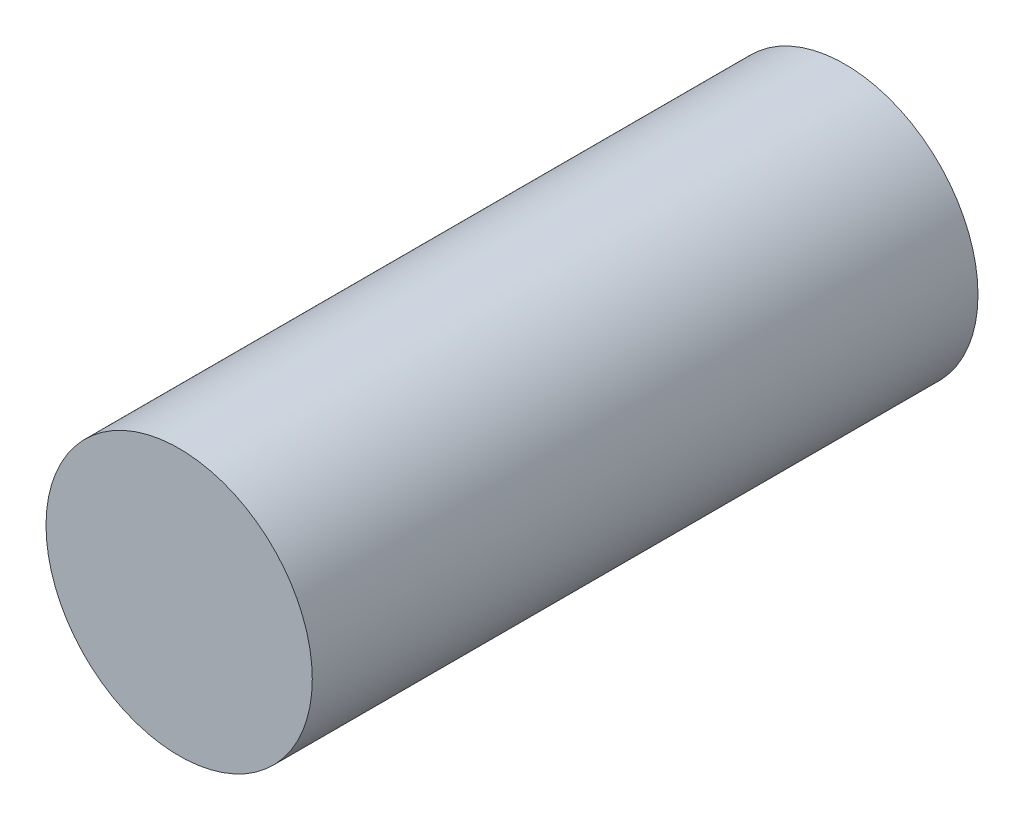
SolidWorks part; units mm, degrees
ref_plane "前视基准面" through (0, 0, 0) normal (0, 0, 1) x (1, 0, 0)
ref_plane "上视基准面" through (0, 0, 0) normal (0, 1, 0) x (1, 0, 0)
ref_plane "右视基准面" through (0, 0, 0) normal (1, 0, 0) x (0, 0, -1)
other "Configuration Table"
sketch "草图1" plane through (0, 0, 0) normal (0, 0, 1) x (1, 0, 0)
  circle A0 centre (0, 0) radius 40
  dimension "D1" = 80
extrude "凸台-拉伸1" add sketch "草图1" along normal blind 200
